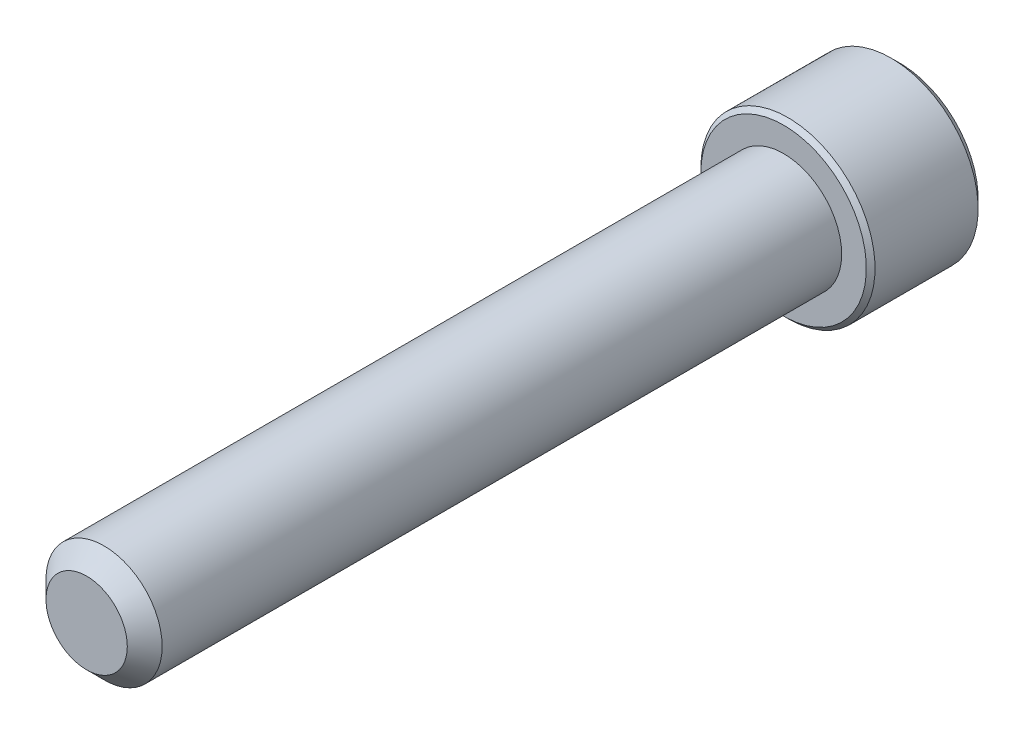
SolidWorks part; units mm, degrees
ref_plane "Front Plane" through (0, 0, 0) normal (0, 0, 1) x (1, 0, 0)
ref_plane "Top Plane" through (0, 0, 0) normal (0, 1, 0) x (1, 0, 0)
ref_plane "Right Plane" through (0, 0, 0) normal (1, 0, 0) x (0, 0, -1)
sketch "Sketch0" plane through (0, 0, 0) normal (1, 0, 0) x (0, 0, -1)
  line L0 (0, 0) -> (38.1, 0) construction
  line L1 (0, -3.175) -> (0, 3.175) construction
  line L2 (44.45, -4.7625) -> (44.45, 4.7625) construction
  line L3 (44.45, -2.3813) -> (44.45, 2.3812) construction
  point P2 (44.45, 0)
  point P4 (25.4, 0)
  point P8 (0, 0)
  point P11 (44.45, 0)
  point P14 (44.45, 0)
  dimension "Min Thread" = 25.4
  dimension "OD" = 6.35
  dimension "screw length" = 38.1
  dimension "head depth" = 6.35
  dimension "head dia" = 9.525
  dimension "hex dia" = 4.7625
sketch "Sketch1" plane through (0, 0, 0) normal (0, 0, 1) x (1, 0, 0)
  circle A0 centre (0, 0) radius 3.175
  dimension "OD" = 6.35
extrude "Extrude1" add sketch "Sketch1" against normal blind 38.1
sketch "Sketch2" [suppressed] plane through (0, 0, 0) normal (0, 0, 1) x (1, 0, 0)
  circle A0 centre (0, 0) radius 3.175 construction
  circle A1 centre (0, 0) radius 3.175
chamfer "Chamfer3" distance 0.9525 angle 45 1 edges at (3.175, 0, 0)
sketch "Sketch3" [suppressed] plane through (0, 0, 0) normal (1, 0, 0) x (0, 0, -1)
  line L0 (-1.1113, 3.175) -> (-0.635, 2.3501)
  line L1 (-0.635, 2.3501) -> (-0.4763, 2.3501)
  line L2 (-0.4763, 2.3501) -> (0, 3.175)
  line L3 (-1.1113, 3.175) -> (0, 3.175)
  line L4 (-0.5556, 3.175) -> (-0.5556, 2.3501) construction
  line L5 (-0.8731, 2.7626) -> (-0.2381, 2.7626) construction
  line L6 (0, 3.175) -> (0, -3.175) construction
  dimension "D1" = 0.1588
  dimension "D2" = 0.635
  dimension "D3" = 60
sketch "Sketch6" plane through (0, 0, -38.1) normal (0, 0, -1) x (-1, 0, 0)
  circle A0 centre (0, 0) radius 4.7625
  dimension "head dia" = 9.525
extrude "Extrude2" add sketch "Sketch6" along normal blind 6.35
sketch "Sketch7" plane through (0, 0, -44.45) normal (0, 0, -1) x (-1, 0, 0)
  line L1 (0, 2.7496) -> (-2.3812, 1.3748)
  line L2 (-2.3812, 1.3748) -> (-2.3812, -1.3748)
  line L3 (-2.3812, -1.3748) -> (0, -2.7496)
  line L4 (0, -2.7496) -> (2.3812, -1.3748)
  line L5 (2.3812, -1.3748) -> (2.3812, 1.3748)
  line L6 (2.3812, 1.3748) -> (0, 2.7496)
  circle A0 centre (0, 0) radius 2.3813 construction
  dimension "hex dia" = 4.7625
extrude "Cut-Extrude1" cut sketch "Sketch7" against normal blind 3.5719
sketch "Sketch8" plane through (0, 0, -44.45) normal (0, 0, -1) x (-1, 0, 0)
  circle A0 centre (0, 0) radius 2.7496
extrude "Cut-Extrude2" cut sketch "Sketch8" against normal through all draft 45
chamfer "Chamfer1" distance 0.4763 angle 45 1 edges at (-4.7625, 0, -44.45)
chamfer "Chamfer2" distance 0.2381 angle 45 1 edges at (-4.7625, 0, -38.1)
sketch "Sketch9" plane through (0, 0, 0) normal (1, 0, 0) x (0, 0, -1)
  line L0 (44.45, -4.7625) -> (44.45, 4.7625) construction
  line L2 (38.1, -4.7625) -> (38.1, 4.7625) construction
  line L9 (43.9738, 4.7625) -> (38.3381, 4.7625) construction
  line L10 (0, -3.175) -> (0, 3.175) construction
  line L11 (0, -3.175) -> (0, 3.175)
  line L12 (3.175, -3.175) -> (3.175, 3.175) construction
  point P4 (44.45, 0)
  point P6 (38.1, 0)
  point P14 (3.175, 0)
  point P15 (3.175, -3.175)
  dimension "D1" = 3.175
ref_plane "Contact Plane 1" through (0, 0, -38.1) normal (0, 0, 1) x (1, 0, 0)
ref_axis "Center Axis 1" through (0, 0, 9.7485) along (0, 0, -1)
curve "Helix/Spiral1" [suppressed] pitch 1.27 height 39.37 turns 31 parameters "pitch"=1.27
sweep "Cut-Sweep1" [suppressed] cut profiles "Sketch3" path "Helix/Spiral1"
sketch "Sketch5" [suppressed] plane through (0, 0, 0) normal (1, 0, 0) x (0, 0, -1)
  line L1 (38.1254, 3.175) -> (25.4, 3.175)
  line L2 (38.1254, 3.175) -> (38.1254, 0)
  line L3 (38.1254, 0) -> (24.2444, 0)
  line L4 (0, 0) -> (38.1, 0) construction
  line L5 (25.4, 3.175) -> (24.2444, 0)
  line L6 (0, 0) -> (44.45, 0) construction
  dimension "D1" = 70
  dimension "D3" = 6.3246
revolve "partially thread" [suppressed] add sketch "Sketch5" angle 360 about L6
sketch "Sketch10" [suppressed] plane through (0, 0, -38.1) normal (0, 0, 1) x (1, 0, 0)
  line L0 (-0.5125, 5.0006) -> (0, 4.5244)
  line L1 (0, 4.5244) -> (0.5125, 5.0006)
  line L2 (0, 4.5244) -> (0, 5.0006) construction
  line L3 (-0.5125, 5.0006) -> (0.5125, 5.0006)
  line L4 (0, -5.2316) -> (0, 5.2316) construction
  line L5 (0, 0) -> (0.2492, 4.756) construction
  line L6 (-0.2492, 4.756) -> (0, 0) construction
  circle A2 centre (0, 0) radius 4.7625 construction
  circle A5 centre (0, 0) radius 4.5244 construction
  dimension "D1" = 6
  dimension "D2" = 0.4762
extrude "Cut-Extrude3" [suppressed] cut sketch "Sketch10" against normal through all
pattern_circular "CirPattern1" [suppressed] count 60 over 360 of bodies 108
equation "\"D3@Helix/Spiral1\"=\"pitch@Helix/Spiral1\"+\"screw length@Sketch0\""
equation "\"D1@Sketch3\" = \"pitch@Helix/Spiral1\"*.125"
equation "\"D2@Sketch3\" = \"pitch@Helix/Spiral1\"*.5"
equation "\"D1@Cut-Extrude1\"=\"hex dia@Sketch0\"*.75"
equation "\"D1@Chamfer1\"=\"head dia@Sketch0\"*.05"
equation "\"D1@Chamfer2\" = \"D1@Chamfer1\"/2"
equation "\"D1@Chamfer3\" = \"pitch@Helix/Spiral1\"*.750"
equation "\"D2@Sketch10\"=\"D1@Chamfer1\""
equation "\"D1@CirPattern1\"=\"D3@CirPattern1\"/\"D1@Sketch10\""
equation "\"D1@Sketch9\"=\"pitch@Helix/Spiral1\"*2.5"
equation "\"OD@Sketch1\"=\"OD@Sketch0\""
equation "\"screw length@Extrude1\"=\"screw length@Sketch0\""
equation "\"head depth@Extrude2\"=\"head depth@Sketch0\""
equation "\"head dia@Sketch6\"=\"head dia@Sketch0\""
equation "\"hex dia@Sketch7\"=\"hex dia@Sketch0\""
equation "\"D3@Sketch5\"=\"head depth@Sketch0\"-.001"
